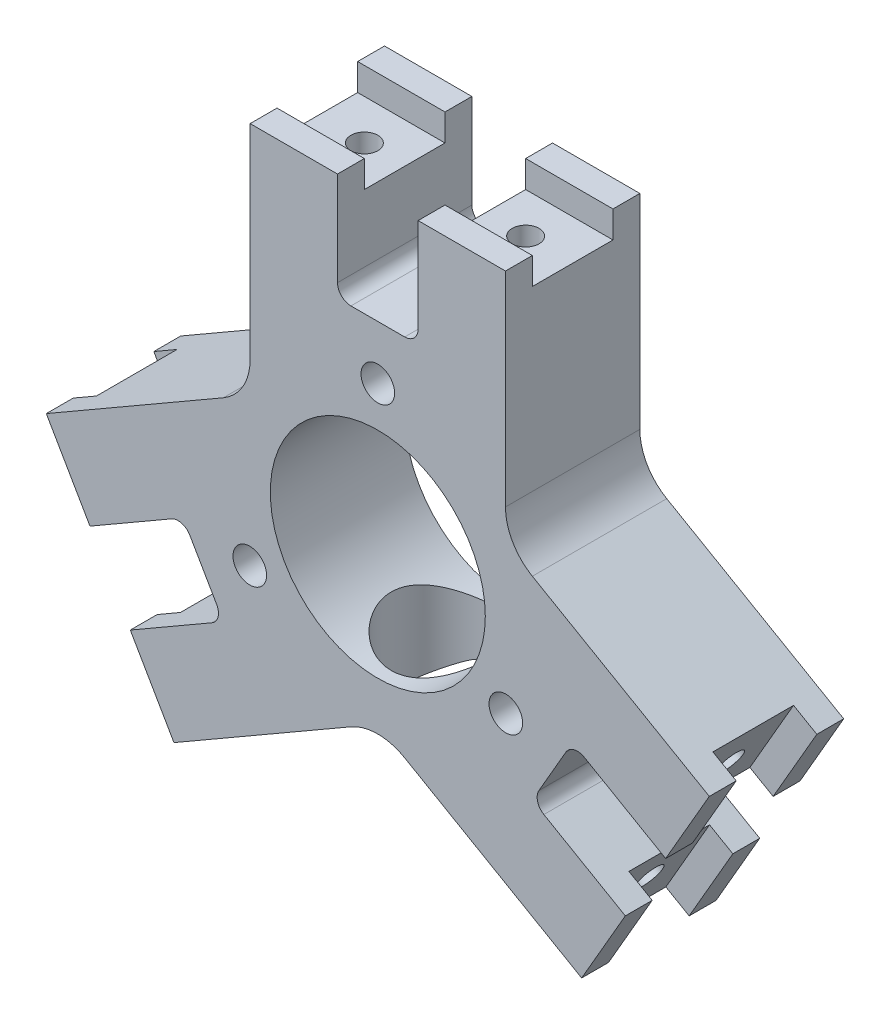
SolidWorks part; units mm, degrees
ref_plane "Plan de face" through (0, 0, 0) normal (0, 0, 1) x (1, 0, 0)
ref_plane "Plan de dessus" through (0, 0, 0) normal (0, 1, 0) x (1, 0, 0)
ref_plane "Plan de droite" through (0, 0, 0) normal (1, 0, 0) x (0, 0, -1)
sketch "Esquisse1" plane through (0, 0, 0) normal (0, 0, 1) x (1, 0, 0)
  line L0 (24.6686, -3.2728) -> (21.4186, -8.9019)
  line L1 (-9.5, 23) -> (-3, 23)
  line L2 (-9.5, 23) -> (-9.5, 7.7942)
  line L3 (-3, 16) -> (-3, 23)
  line L4 (9.5, 23) -> (9.5, 7.7942)
  line L5 (24.6686, -3.2728) -> (11.5, 4.3301)
  line L6 (15.1686, -19.7272) -> (2, -12.1244)
  line L7 (-2, 15) -> (2, 15)
  line L8 (-15.1686, -19.7272) -> (-18.4186, -14.0981)
  line L9 (-15.1686, -19.7272) -> (-2, -12.1244)
  line L10 (-24.6686, -3.2728) -> (-11.5, 4.3301)
  line L11 (-21.4186, -8.9019) -> (-24.6686, -3.2728)
  line L12 (3, 16) -> (3, 23)
  line L13 (8, 0) -> (9.5, 0)
  line L14 (-3, 15) -> (3, 23) construction
  line L16 (-3, 23) -> (3, 15) construction
  line L17 (0, 0) -> (0, 30.6728) construction
  line L18 (0, 0) -> (26.5634, -15.3364) construction
  line L19 (0, 0) -> (-26.5634, -15.3364) construction
  line L20 (15.3564, -5.4019) -> (21.4186, -8.9019)
  line L21 (13.9904, -5.7679) -> (11.9904, -9.2321)
  line L22 (12.3564, -10.5981) -> (18.4186, -14.0981)
  line L23 (-12.3564, -10.5981) -> (-18.4186, -14.0981)
  line L24 (-11.9904, -9.2321) -> (-13.9904, -5.7679)
  line L25 (-15.3564, -5.4019) -> (-21.4186, -8.9019)
  line L26 (3, 23) -> (9.5, 23)
  line L27 (18.4186, -14.0981) -> (15.1686, -19.7272)
  circle A0 centre (0, 0) radius 8
  arc A1 (-2, -12.1244) -> (2, -12.1244) centre (0, -15.5885) cw
  arc A2 (11.5, 4.3301) -> (9.5, 7.7942) centre (13.5, 7.7942) cw
  arc A3 (-9.5, 7.7942) -> (-11.5, 4.3301) centre (-13.5, 7.7942) cw
  circle A4 centre (0, 0) radius 11 construction
  circle A5 centre (0, 11) radius 1.25
  circle A6 centre (9.5263, -5.5) radius 1.25
  circle A7 centre (-9.5263, -5.5) radius 1.25
  arc A8 (11.9904, -9.2321) -> (12.3564, -10.5981) centre (12.8564, -9.7321) ccw
  arc A9 (15.3564, -5.4019) -> (13.9904, -5.7679) centre (14.8564, -6.2679) ccw
  arc A10 (-12.3564, -10.5981) -> (-11.9904, -9.2321) centre (-12.8564, -9.7321) ccw
  arc A11 (-13.9904, -5.7679) -> (-15.3564, -5.4019) centre (-14.8564, -6.2679) ccw
  arc A12 (2, 15) -> (3, 16) centre (2, 16) ccw
  arc A13 (-2, 15) -> (-3, 16) centre (-2, 16) cw
  point P7 (0, 0)
  point P12 (0, 19)
  point P19 (0, 0)
  point P36 (0, 0)
  point P45 (0, 0)
  point P52 (0, 0)
  dimension "D3" = 16
  dimension "D5" = 4
  dimension "D8" = 22
  dimension "D11" = 2.5
  dimension "D13" = 1
  dimension "D1" = 19
  dimension "D2" = 8
  dimension "D6" = 6
  dimension "D7" = 23
  dimension "D4" = 3
  dimension "D9" = 3
  dimension "D10" = 3
  dimension "D12" = 3
extrude "Boss.-Extru.1" add sketch "Esquisse1" along normal blind 5 and the other way blind 5 contours L2 A3 L10 L11 L25 L24 L23 L8 L9 A1 L6 L27 L22 L21 L20 L0 L5 A2 L4 L26 L12 L7 L3 L1 A7 A6 A5 A0 region at (22.4784, -5.761, 0)
sketch "Esquisse2" plane through (-9.5, 0, 0) normal (-1, 0, 0) x (0, 0, 1)
  line L0 (0, 23) -> (0, 15.3642) construction
  line L1 (5, 23) -> (-5, 23) construction
  line L2 (-3, 21) -> (-3, 23)
  line L3 (-3, 21) -> (3, 21)
  line L4 (-3, 23) -> (3, 23)
  line L5 (3, 21) -> (3, 23)
  line L6 (-3, 21) -> (3, 23) construction
  line L7 (-3, 23) -> (3, 21) construction
  point P5 (0, 22)
  dimension "D1" = 2
  dimension "D2" = 6
extrude "Enlèv. mat.-Extru.1" cut sketch "Esquisse2" against normal blind 19
sketch "Esquisse3" plane through (0, 21, 0) normal (0, 1, 0) x (1, 0, 0)
  line L1 (-6, 0) -> (6, 0) construction
  line L2 (-6, 3) -> (-6, -3) construction
  line L3 (-3, 3) -> (-9.5, 3) construction
  line L4 (-3, -3) -> (-9.5, -3) construction
  circle A0 centre (-6, 0) radius 1
  circle A1 centre (6, 0) radius 1
  dimension "D1" = 2
  dimension "D2" = 2
  dimension "D3" = 12
extrude "Enlèv. mat.-Extru.2" cut sketch "Esquisse3" against normal blind 5
pattern_circular "Répétition circulaire1" count 3 over 360 about axis through (0, 0, -5) along (0, 0, 1) of "Enlèv. mat.-Extru.2", "Enlèv. mat.-Extru.1"
sketch "Esquisse5" plane through (0, 0, 0) normal (0, 1, 0) x (1, 0, 0)
  circle A0 centre (0, 0) radius 4
  dimension "D1" = 8
extrude "Enlèv. mat.-Extru.5" cut sketch "Esquisse5" against normal blind 18
